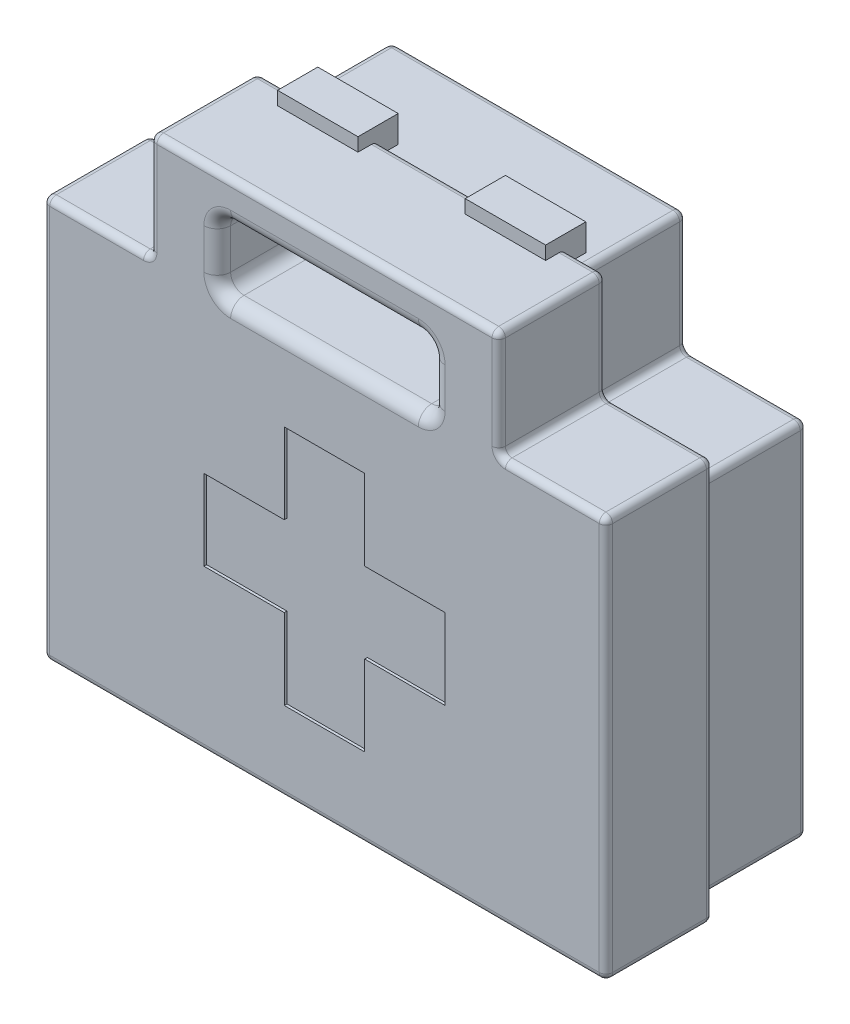
SolidWorks part; units mm, degrees
ref_plane "Front" through (0, 0, 0) normal (0, 0, 1) x (1, 0, 0)
ref_plane "Top" through (0, 0, 0) normal (0, 1, 0) x (1, 0, 0)
ref_plane "Right" through (0, 0, 0) normal (1, 0, 0) x (0, 0, -1)
sketch "Sketch1" plane through (0, 0, 0) normal (0, 0, 1) x (1, 0, 0)
  line L1 (0, 0) -> (200, 0)
  line L2 (0, 0) -> (0, 180)
  line L3 (0, 180) -> (200, 180)
  line L4 (200, 0) -> (200, 180)
  dimension "D1" = 200
  dimension "D2" = 180
extrude "Boss-Extrude1" add sketch "Sketch1" along normal blind 40
sketch "Sketch2" plane through (0, 0, 40) normal (0, 0, 1) x (1, 0, 0)
  line L0 (200, 0) -> (200, 180) construction
  line L1 (140, 170) -> (60, 170)
  line L2 (140, 170) -> (140, 145)
  line L3 (140, 145) -> (60, 145)
  line L4 (60, 170) -> (60, 145)
  line L5 (0, 180) -> (0, 0) construction
  line L6 (200, 180) -> (0, 180) construction
  dimension "D1" = 60
  dimension "D2" = 60
  dimension "D3" = 10
  dimension "D4" = 25
extrude "Cut-Extrude1" cut sketch "Sketch2" against normal through all
sketch "Sketch3" plane through (0, 0, 40) normal (0, 0, 1) x (1, 0, 0)
  line L0 (0, 0) -> (200, 0) construction
  line L1 (205, -5) -> (-5, -5)
  line L2 (205, -5) -> (205, 185)
  line L3 (205, 185) -> (-5, 185)
  line L4 (-5, -5) -> (-5, 185)
  line L5 (200, 0) -> (200, 180) construction
  line L6 (0, 180) -> (0, 0) construction
  line L7 (200, 180) -> (0, 180) construction
  dimension "D1" = 5
  dimension "D2" = 5
  dimension "D3" = 5
  dimension "D4" = 5
extrude "Boss-Extrude2" add sketch "Sketch3" along normal blind 40
extrude "Cut-Extrude2" cut sketch "Sketch2<2>" along normal through all
sketch "Sketch2<2>" plane through (0, 0, 40) normal (0, 0, 1) x (1, 0, 0) same geometry as "Sketch2"
sketch "Sketch4" plane through (0, 180, 0) normal (0, 1, 0) x (1, 0, 0)
  line L0 (200, -40) -> (200, 0) construction
  line L1 (150, -32.5) -> (120, -32.5)
  line L2 (150, -32.5) -> (150, -47.5)
  line L3 (150, -47.5) -> (120, -47.5)
  line L4 (120, -32.5) -> (120, -47.5)
  line L5 (80, -47.5) -> (50, -47.5)
  line L6 (80, -47.5) -> (80, -32.5)
  line L7 (80, -32.5) -> (50, -32.5)
  line L8 (50, -47.5) -> (50, -32.5)
  line L9 (205, -40) -> (-5, -40) construction
  line L10 (0, -40) -> (0, 0) construction
  dimension "D1" = 50
  dimension "D2" = 30
  dimension "D3" = 15
  dimension "D4" = 7.5
  dimension "D5" = 30
  dimension "D6" = 50
  dimension "D7" = 7.5
  dimension "D8" = 7.5
extrude "Boss-Extrude3" add sketch "Sketch4" along normal blind 10
sketch "Sketch5" plane through (0, 0, 80) normal (0, 0, 1) x (1, 0, 0)
  line L0 (205, 185) -> (-5, 185) construction
  line L1 (205, 185) -> (165, 185)
  line L2 (205, 185) -> (205, 145)
  line L3 (205, 145) -> (165, 145)
  line L4 (165, 185) -> (165, 145)
  line L6 (35, 145) -> (-5, 145)
  line L7 (35, 145) -> (35, 185)
  line L8 (35, 185) -> (-5, 185)
  line L9 (-5, 145) -> (-5, 185)
  dimension "D1" = 40
  dimension "D2" = 40
  dimension "D3" = 40
  dimension "D4" = 40
extrude "Cut-Extrude3" cut sketch "Sketch5" against normal blind 40
sketch "Sketch6" plane through (0, 0, 0) normal (0, 0, -1) x (-1, 0, 0)
  line L0 (-200, 180) -> (0, 180) construction
  line L1 (-200, 180) -> (-155, 180)
  line L2 (-200, 180) -> (-200, 135)
  line L3 (-200, 135) -> (-155, 135)
  line L4 (-155, 180) -> (-155, 135)
  line L5 (0, 180) -> (-45, 180)
  line L6 (0, 180) -> (0, 135)
  line L7 (0, 135) -> (-45, 135)
  line L8 (-45, 180) -> (-45, 135)
  line L9 (0, 180) -> (0, 0) construction
  dimension "D1" = 45
  dimension "D2" = 45
  dimension "D3" = 45
  dimension "D4" = 45
extrude "Cut-Extrude4" cut sketch "Sketch6" against normal blind 40
fillet "Fillet1" radius 5 12 edges at (140, 157.5, 0) (140, 157.5, 80) (100, 145, 0) (140, 145, 40) (100, 145, 80) (60, 157.5, 0) (60, 145, 40) (60, 157.5, 80) (100, 170, 0) (60, 170, 40) (100, 170, 80) (140, 170, 40)
fillet "Fillet2" radius 2.5 52 edges at (0, 0, 20) (200, 0, 20) (0, 67.5, 0) (100, 0, 0) (200, 67.5, 0) (100, 180, 0) (-5, -5, 60) (205, -5, 60) (205, 70, 80) (100, -5, 80) (-5, 70, 80) (100, 185, 80) (100, 180, 40) (100, 185, 40) (205, 145, 60) (185, 145, 80) (165, 185, 60) (165, 145, 60) (165, 165, 80) (35, 185, 60) (35, 165, 80) (-5, 145, 60) (35, 145, 60) (15, 145, 80) (200, 67.5, 40) (100, 0, 40) (0, 67.5, 40) (42.5, 185, 40) (35, 165, 40) (15, 145, 40) (-5, 70, 40) (100, -5, 40) (205, 70, 40) (185, 145, 40) (165, 165, 40) (157.5, 185, 40) (155, 157.5, 40) (155, 180, 20) (155, 157.5, 0) (200, 135, 20) (177.5, 135, 40) (155, 135, 20) (177.5, 135, 0) (22.5, 135, 40) (0, 135, 20) (22.5, 135, 0) (45, 180, 20) (45, 157.5, 40) (45, 135, 20) (45, 157.5, 0) (152.5, 180, 40) (47.5, 180, 40)
sketch "Sketch7" plane through (0, 0, 80) normal (0, 0, 1) x (1, 0, 0)
  line L0 (202.5, -2.5) -> (202.5, 142.5) construction
  line L1 (145, 55) -> (55, 55)
  line L2 (145, 55) -> (145, 85)
  line L3 (145, 85) -> (55, 85)
  line L4 (55, 55) -> (55, 85)
  line L5 (115, 25) -> (85, 25)
  line L6 (115, 25) -> (115, 115)
  line L7 (115, 115) -> (85, 115)
  line L8 (85, 25) -> (85, 115)
  line L10 (135, 140) -> (65, 140) construction
  dimension "D1" = 30
  dimension "D2" = 30
  dimension "D3" = 90
  dimension "D4" = 90
  dimension "D5" = 30
  dimension "D6" = 30
  dimension "D7" = 57.5
  dimension "D8" = 25
extrude "Cut-Extrude5" cut sketch "Sketch7" against normal blind 1 contours L8 L1 L6 L3 | L6 L1 L2 L3 | L8 L5 L6 L1 | L1 L8 L3 L4 | L8 L3 L6 L7 region at (130, 70, 80) region at (100, 40, 80) region at (100, 70, 80) region at (70, 70, 80) region at (100, 100, 80)
